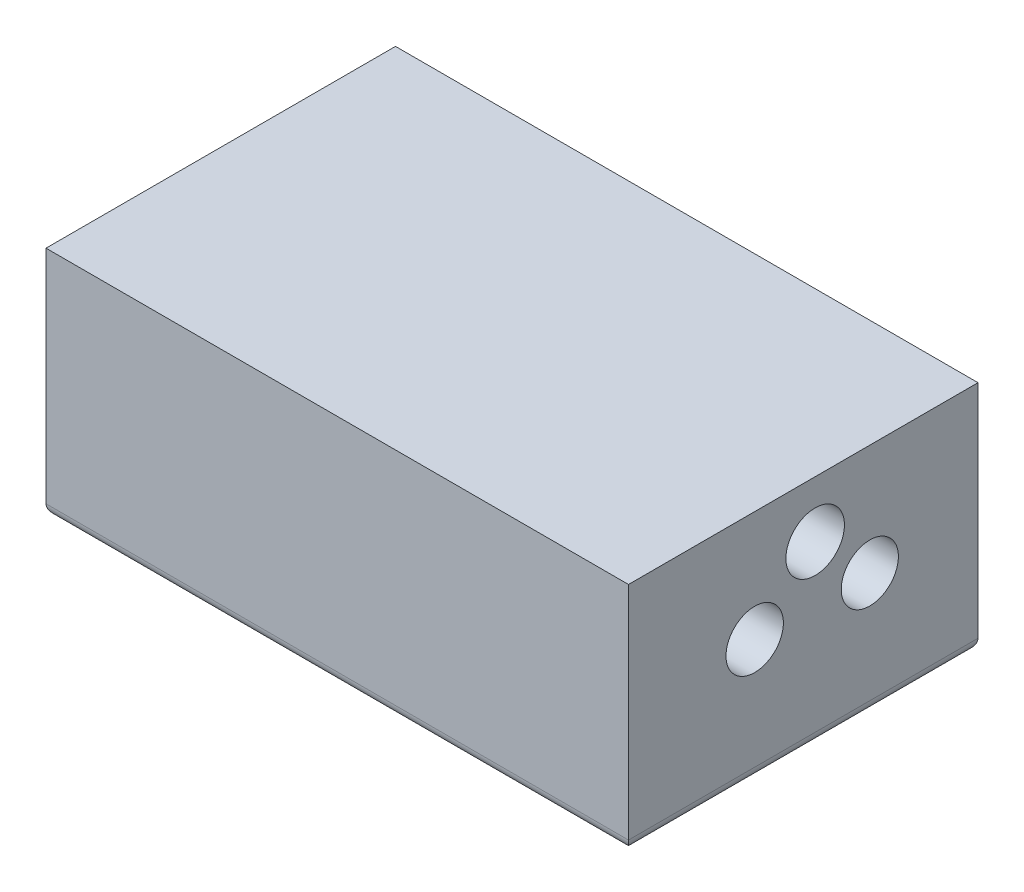
SolidWorks part; units mm, degrees
ref_plane "Front Plane" through (0, 0, 0) normal (0, 0, 1) x (1, 0, 0)
ref_plane "Top Plane" through (0, 0, 0) normal (0, 1, 0) x (1, 0, 0)
ref_plane "Right Plane" through (0, 0, 0) normal (1, 0, 0) x (0, 0, -1)
sketch "Sketch2" plane through (0, 0, 0) normal (0, 1, 0) x (1, 0, 0)
  line L1 (-63.5, 38.1) -> (63.5, 38.1)
  line L2 (-63.5, 38.1) -> (-63.5, -38.1)
  line L3 (-63.5, -38.1) -> (63.5, -38.1)
  line L4 (63.5, 38.1) -> (63.5, -38.1)
  dimension "D1" = 127
  dimension "D2" = 76.2
extrude "Boss-Extrude1" add sketch "Sketch2" along normal blind 50.8
ref_plane "Logo  Plane" through (0, 0, 0) normal (0, -1, 0) x (-1, 0, 0)
sketch "Sketch12" plane through (0, 0, 0) normal (0, -1, 0) x (-1, 0, 0)
  point P0 (-27.3933, -17.3606)
sketch_block_instance "Logo-1"
sketch_block "Block4"
ref_plane "Plane3" through (63.5, 0, 0) normal (1, 0, 0) x (0, 0, -1)
sketch "Sketch17" plane through (63.5, 0, 0) normal (1, 0, 0) x (0, 0, -1)
  circle A0 centre (14.5124, 26.67) radius 6.234
  circle A1 centre (-10.5869, 26.67) radius 6.2602
shell "Shell20" thickness 79.6787 rebuild error yes
extrude "Cut-Extrude4" cut sketch "Sketch17" against normal blind 15.24 contours A1 | A0
sketch "Sketch18" plane through (63.5, 0, 0) normal (1, 0, 0) x (0, 0, -1)
  circle A0 centre (2.5981, 38.5287) radius 6.3824
extrude "Cut-Extrude5" cut sketch "Sketch18" against normal blind 10.16
sketch "Sketch19" plane through (0, 0, 0) normal (0, -1, 0) x (1, 0, 0)
  line L0 (-63.5, 38.1) -> (63.5, 38.1) construction
  line L1 (-28.2105, 38.1) -> (-31.8007, 38.1)
  line L2 (-28.2105, 38.1) -> (-28.2105, -38.1)
  line L3 (-28.2105, -38.1) -> (-31.8007, -38.1)
  line L4 (-31.8007, 38.1) -> (-31.8007, -38.1)
  line L5 (63.5, -38.1) -> (-63.5, -38.1) construction
extrude "Boss-Extrude2" add sketch "Sketch19" against normal blind 30.48
sketch "Sketch20" plane through (0, 0, 0) normal (0, -1, 0) x (1, 0, 0)
  line L0 (-63.5, 38.1) -> (63.5, 38.1) construction
  line L1 (-44.8542, 38.1) -> (-38.519, 38.1)
  line L2 (-44.8542, 38.1) -> (-44.8542, -38.1)
  line L3 (-44.8542, -38.1) -> (-38.519, -38.1)
  line L4 (-38.519, 38.1) -> (-38.519, -38.1)
  line L5 (63.5, -38.1) -> (-63.5, -38.1) construction
extrude "Boss-Extrude3" add sketch "Sketch20" against normal blind 25.4
sketch "Sketch21" plane through (-63.5, 0, 0) normal (-1, 0, 0) x (0, 0, 1)
  line L0 (38.1, 50.8) -> (38.1, 0) construction
  line L1 (38.1, 25.4) -> (-38.1, 25.4)
  line L2 (38.1, 25.4) -> (38.1, 31.089)
  line L3 (38.1, 31.089) -> (-38.1, 31.089)
  line L4 (-38.1, 25.4) -> (-38.1, 31.089)
  line L5 (-38.1, 50.8) -> (-38.1, 0) construction
extrude "Boss-Extrude4" add sketch "Sketch21" against normal blind 25.4
sketch "Sketch23" plane through (63.5, 0, 0) normal (1, 0, 0) x (0, 0, -1)
  line L0 (14.5124, 26.67) -> (-9.3162, 26.67) construction
  point P4 (2.5981, 38.5287)
  point P5 (2.5981, 26.67)
  point P7 (124.574, 65.619)
fillet "Fillet1" radius 2.54 4 edges at (0, 0, -38.1) (-63.5, 0, 0) (0, 0, 38.1) (63.5, 0, 0)
